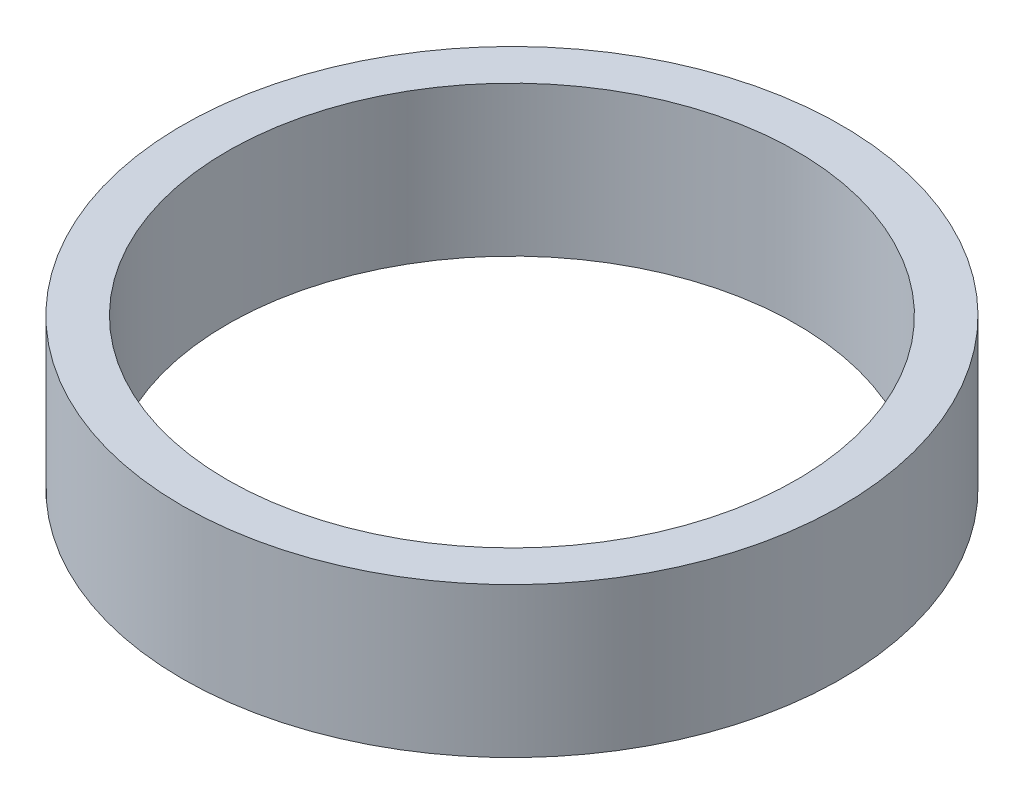
SolidWorks part; units mm, degrees
ref_plane "Front Plane" through (0, 0, 0) normal (0, 0, 1) x (1, 0, 0)
ref_plane "Top Plane" through (0, 0, 0) normal (0, 1, 0) x (1, 0, 0)
ref_plane "Right Plane" through (0, 0, 0) normal (1, 0, 0) x (0, 0, -1)
sketch "Sketch1" plane through (0, 0, 0) normal (0, 1, 0) x (1, 0, 0)
  circle A0 centre (0, 0) radius 55
  dimension "FLANGE_OD" = 110
extrude "Boss-Extrude1" add sketch "Sketch1" along normal blind 25
sketch "Sketch2" plane through (0, 0, 0) normal (0, 1, 0) x (1, 0, 0)
  circle A0 centre (0, 0) radius 47.5
  dimension "BORE_D" = 95
extrude "Cut-Extrude1" cut sketch "Sketch2" along normal through all
sketch "Sketch3" plane through (0, 25, 0) normal (0, 1, 0) x (1, 0, 0)
  circle A0 centre (0, 0) radius 25.5852 construction
  circle A1 centre (-25.5852, 0) radius 1.5
  dimension "BOLT_D" = 3
  dimension "BOLT_PCD" = 51.1704
extrude "Cut-Extrude2" cut sketch "Sketch3" against normal blind 16.1541 rebuild error yes
pattern_circular "CirPattern1" count 4 over 360 rebuild error yes
